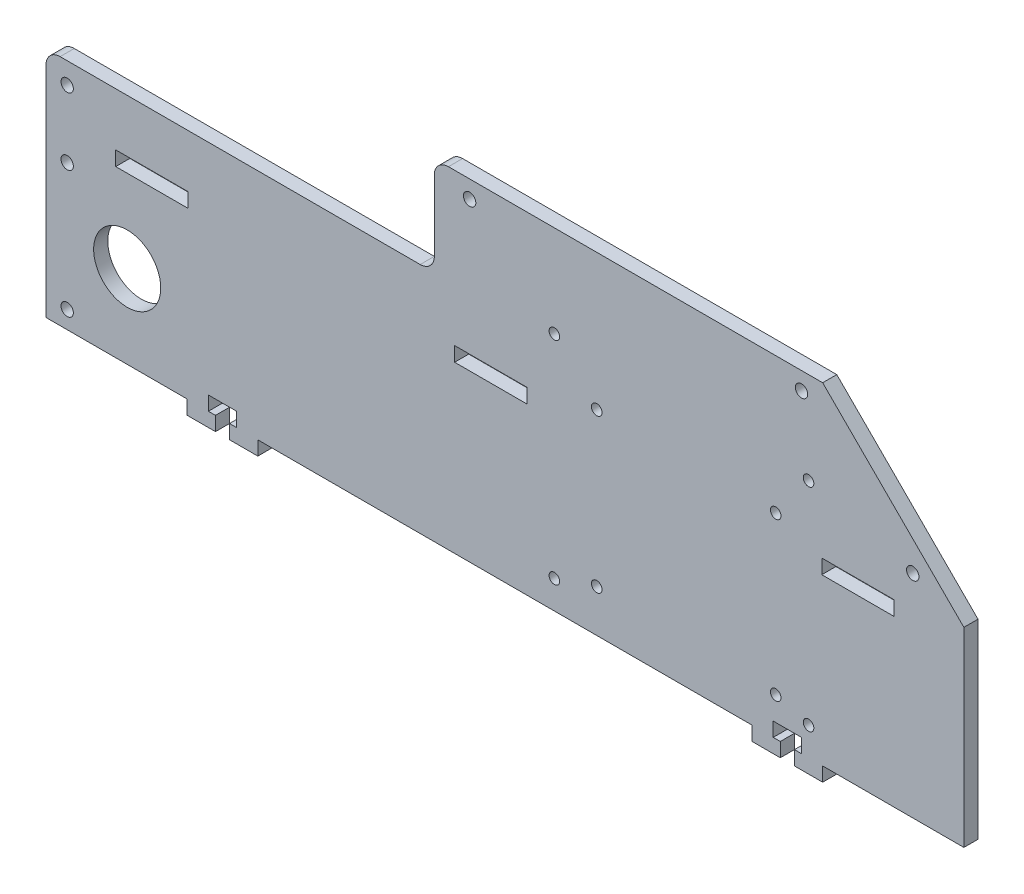
SolidWorks part; units mm, degrees
ref_plane "Спереди" through (0, 0, 0) normal (0, 0, 1) x (1, 0, 0)
ref_plane "Сверху" through (0, 0, 0) normal (0, 1, 0) x (1, 0, 0)
ref_plane "Справа" through (0, 0, 0) normal (1, 0, 0) x (0, 0, -1)
other "Configuration Table"
sketch "Эскиз1" plane through (0, 0, 0) normal (0, 0, 1) x (1, 0, 0)
  line L0 (52, -59) -> (60, -59)
  line L2 (0, 0) -> (0, -55)
  line L3 (0, -55) -> (40, -55)
  line L4 (260, -1) -> (260, -55)
  line L6 (40, -55) -> (40, -59)
  line L7 (40, -59) -> (48, -59)
  line L8 (60, -55) -> (60, -59)
  line L10 (200, -55) -> (200, -59)
  line L11 (200, -59) -> (208, -59)
  line L12 (220, -55) -> (220, -59)
  line L14 (48, -59) -> (48, -55)
  line L16 (52, -59) -> (52, -55)
  line L18 (46, -55) -> (46, -51)
  line L19 (46, -51) -> (54, -51)
  line L20 (54, -55) -> (54, -51)
  line L21 (46, -55) -> (48, -55)
  line L23 (52, -55) -> (54, -55)
  line L24 (60, -55) -> (200, -55)
  line L25 (206, -55) -> (208, -55)
  line L26 (212, -55) -> (214, -55)
  line L28 (208, -55) -> (208, -59)
  line L30 (212, -55) -> (212, -59)
  line L32 (206, -55) -> (206, -51)
  line L33 (206, -51) -> (214, -51)
  line L34 (214, -55) -> (214, -51)
  line L35 (220, -55) -> (260, -55)
  line L36 (120, 39) -> (220, 39)
  line L37 (19.75, -4) -> (40.25, -4)
  line L38 (19.75, -4) -> (19.75, -8.1)
  line L39 (212, -59) -> (220, -59)
  line L40 (19.75, -8.1) -> (40.25, -8.1)
  line L41 (40.25, -4) -> (40.25, -8.1)
  line L42 (219.75, -4.119) -> (240.25, -4.119)
  line L43 (219.75, -4.119) -> (219.75, -8.219)
  line L44 (219.75, -8.219) -> (240.25, -8.219)
  line L45 (240.25, -4.119) -> (240.25, -8.219)
  line L46 (115.75, -4) -> (136.25, -4)
  line L47 (115.75, -4) -> (115.75, -8.1)
  line L48 (115.75, -8.1) -> (136.25, -8.1)
  line L49 (136.25, -4) -> (136.25, -8.1)
  line L51 (0, 0) -> (0, 7)
  line L52 (4, 11) -> (106, 11)
  line L54 (114, 39) -> (120, 39)
  line L63 (110, 15) -> (110, 35)
  line L64 (260, -1) -> (220, 39)
  circle A0 centre (23, -31.5) radius 9.5
  arc A2 (106, 11) -> (110, 15) centre (106, 15) ccw
  arc A3 (110, 35) -> (114, 39) centre (114, 35) cw
  arc A4 (0, 7) -> (4, 11) centre (4, 7) cw
  circle A5 centre (23, -31.5) radius 17.5 construction
  circle A6 centre (156, -43) radius 1.5
  circle A8 centre (206.7, 0.4) radius 1.5
  circle A9 centre (156, 0.4) radius 1.5
  circle A12 centre (206.7, -43) radius 1.5
  circle A13 centre (206.7, -44.2) radius 1.5
  circle A14 centre (144, -47) radius 1.5
  circle A18 centre (216, -47) radius 1.5
  circle A19 centre (216, 13) radius 1.5
  circle A20 centre (144, 13) radius 1.5
  point P55 (0, 11)
  point P58 (0, -27.5)
  dimension "D28" = 19
  dimension "D38" = 54
  dimension "D39" = 4
  dimension "D42" = 35
  dimension "D43" = 3
  dimension "D49" = 44.6
  dimension "D51" = 3
  dimension "D53" = 3
  dimension "D2" = 55
  dimension "D3" = 4
  dimension "D4" = 20
  dimension "D5" = 40
  dimension "D6" = 4
  dimension "D7" = 20
  dimension "D8" = 40
  dimension "D9" = 4
  dimension "D10" = 2
  dimension "D11" = 2
  dimension "D12" = 4
  dimension "D13" = 8
  dimension "D14" = 4
  dimension "D15" = 8
  dimension "D16" = 4
  dimension "D17" = 2
  dimension "D18" = 2
  dimension "D19" = 4.1
  dimension "D20" = 28
  dimension "D21" = 19.75
  dimension "D22" = 20.5
  dimension "D23" = 4.1
  dimension "D24" = 20.5
  dimension "D25" = 115.75
  dimension "D26" = 19.75
  dimension "D27" = 20.5
  dimension "D29" = 23.5
  dimension "D30" = 23
  dimension "D31" = 4
  dimension "D32" = 110
  dimension "D33" = 66
  dimension "D34" = 94
  dimension "D35" = 40
  dimension "D36" = 260
  dimension "D40" = 40
  dimension "D41" = 220
  dimension "D44" = 12
  dimension "D47" = 156
  dimension "D48" = 43.4
  dimension "D50" = 50.7
  dimension "D52" = 8
  dimension "D55" = 12
  dimension "D45" = 2
  dimension "D46" = 2
  dimension "D56" = 2
base flange "Базовая кромка1" sketch "Эскиз1" thickness 4 reverse thickness direction no parameters "D1"=0.7366
sketch "Эскиз6" plane through (0, 0, 0) normal (0, 0, 1) x (1, 0, 0)
  line L1 (0, 7) -> (0, -55) construction
  line L2 (0, 7) -> (0, -55) construction
  line L3 (0, -55) -> (40, -55) construction
  line L4 (0, -55) -> (40, -55) construction
  line L5 (220, 39) -> (114, 39) construction
  line L7 (260, -1) -> (220, 39) construction
  circle A0 centre (6, 5) radius 1.75
  circle A1 centre (120, 34) radius 1.75
  circle A2 centre (214, 34) radius 1.75
  circle A3 centre (245.5147, 5) radius 1.75
  circle A4 centre (6, -14) radius 1.75
  circle A5 centre (6, -50) radius 1.75
  dimension "D2" = 3.5
  dimension "D1" = 41
  dimension "D3" = 6
  dimension "D4" = 6
  dimension "D5" = 120
  dimension "D6" = 6
  dimension "D7" = 5
  dimension "D8" = 60
  dimension "D9" = 5
  dimension "D10" = 5
  dimension "D11" = 114
  dimension "D12" = 29
  dimension "D13" = 94
  dimension "D14" = 239.5147
  dimension "D15" = 34
  dimension "D16" = 31.5147
extrude "Вырез-Вытянуть1" cut sketch "Эскиз6" against normal through all normal cut yes
sketch "Эскиз7" plane through (0, 0, 0) normal (0, 0, 1) x (1, 0, 0)
  line L0 (19.75, -8.1) -> (40.25, -8.1) construction
  line L1 (64, -16.1) -> (176, -16.1)
  line L2 (60, -20.1) -> (60, -43)
  line L3 (64, -47) -> (176, -47)
  line L4 (180, -20.1) -> (180, -43)
  line L5 (60, -55) -> (200, -55) construction
  line L6 (0, 7) -> (0, -55) construction
  line L7 (260, -55) -> (260, -1) construction
  arc A0 (176, -47) -> (180, -43) centre (176, -43) ccw
  arc A1 (176, -16.1) -> (180, -20.1) centre (176, -20.1) cw
  arc A2 (64, -16.1) -> (60, -20.1) centre (64, -20.1) ccw
  arc A3 (60, -43) -> (64, -47) centre (64, -43) ccw
  dimension "D5" = 4
  dimension "D1" = 8
  dimension "D2" = 8
  dimension "D3" = 60
  dimension "D4" = 80
extrude "Вырез-Вытянуть2" [suppressed] cut sketch "Эскиз7" against normal through all
sketch "Эскиз8" plane through (0, -55, 0) normal (0, -1, 0) x (1, 0, 0)
  line L0 (46, 0) -> (54, 0) construction
  line L1 (48, -4) -> (48, 0) construction
  line L2 (206, 0) -> (214, 0) construction
  line L3 (208, -4) -> (208, 0) construction
  circle A0 centre (210, -2) radius 1
  circle A1 centre (50, -2) radius 0.8222
  dimension "D5" = 2
  dimension "D1" = 2
  dimension "D2" = 2
  dimension "D3" = 2
  dimension "D4" = 2
extrude "Вырез-Вытянуть3" cut sketch "Эскиз8" against normal blind 10 normal cut yes
sketch "Сгиб-Линии1" [suppressed] plane through (0, 0, 0) normal (0, 1, 0) x (1, 0, 0)
sketch "Граничная рамка1" [suppressed] plane through (0, 0, 0) normal (0, 1, 0) x (1, 0, 0)
sheet metal parameters "Листовой металл3" thickness 4 parameters "D1"=0.7366
flat pattern "Развертка3" [suppressed]
sketch "Сгиб-Линии2" plane through (0, 0, 0) normal (0, 1, 0) x (1, 0, 0)
sketch "Граничная рамка2" [suppressed] plane through (0, 0, 0) normal (0, 1, 0) x (1, 0, 0)
sheet metal parameters "Листовой металл4" thickness 4 parameters "D1"=0.7366
flat pattern "Развертка3"
sketch "Сгиб-Линии2" plane through (0, 0, 0) normal (0, 1, 0) x (1, 0, 0)
sketch "Граничная рамка2" [suppressed] plane through (0, 0, 0) normal (0, 1, 0) x (1, 0, 0)
sheet metal parameters "Листовой металл5" thickness 4 parameters "D1"=0.7366
flat pattern "Развертка3"
sketch "Сгиб-Линии2" plane through (0, 0, 0) normal (0, 1, 0) x (1, 0, 0)
sketch "Граничная рамка2" [suppressed] plane through (0, 0, 0) normal (0, 1, 0) x (1, 0, 0)
sheet metal parameters "Листовой металл6" thickness 4 parameters "D1"=0.7366
flat pattern "Развертка3"
sketch "Сгиб-Линии2" plane through (0, 0, 0) normal (0, 1, 0) x (1, 0, 0)
sketch3d "Граничная рамка2" [suppressed]
  line L0 (-3.9999, 32.0001, 0) -> (256, 32, 0) construction
  line L1 (-4, -65.9999, 0) -> (256, -66, 0) construction
  line L2 (-3.9999, 32.0001, 0) -> (-4, -65.9999, 0) construction
  line L3 (256, 32, 0) -> (256, -66, 0) construction
